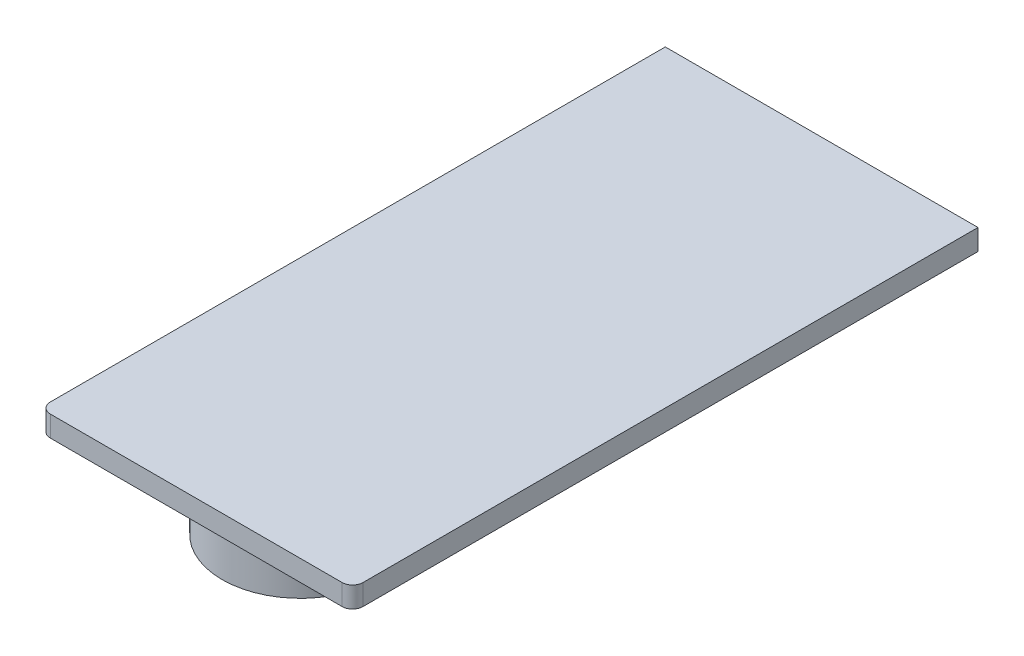
SolidWorks part; units mm, degrees
ref_plane "Front Plane" through (0, 0, 0) normal (0, 0, 1) x (1, 0, 0)
ref_plane "Top Plane" through (0, 0, 0) normal (0, 1, 0) x (1, 0, 0)
ref_plane "Right Plane" through (0, 0, 0) normal (1, 0, 0) x (0, 0, -1)
sketch "Sketch1" plane through (0, 0, 0) normal (0, 1, 0) x (1, 0, 0)
  line L0 (0, 0) -> (0, 76.2)
  line L1 (0, 76.2) -> (38.1, 76.2)
  line L2 (38.1, 76.2) -> (38.1, 0)
  line L3 (38.1, 0) -> (0, 0)
  line L4 (19.05, 0) -> (19.05, 12.7) construction
  circle A0 centre (19.05, 12.7) radius 7.05
  circle A1 centre (19.05, 12.7) radius 9.55
  dimension "D4" = 14.1
  dimension "D5" = 2.5
  dimension "D1" = 76.2
  dimension "D2" = 38.1
  dimension "D3" = 12.7
extrude "Boss-Extrude1" add sketch "Sketch1" along normal blind 2.54 contours L3 L0 L1 L2
extrude "Boss-Extrude2" add sketch "Sketch1<3>" against normal blind 7.62 contours A1 A0 region at (9.7701, 0, -12.7)
sketch "Sketch1<3>" plane through (0, 0, 0) normal (0, 1, 0) x (1, 0, 0) same geometry as "Sketch1"
fillet "Fillet1" radius 1.27 3 edges at (0, 1.27, 0) (38.1, 1.27, 0) (19.05, 0, -22.25)
